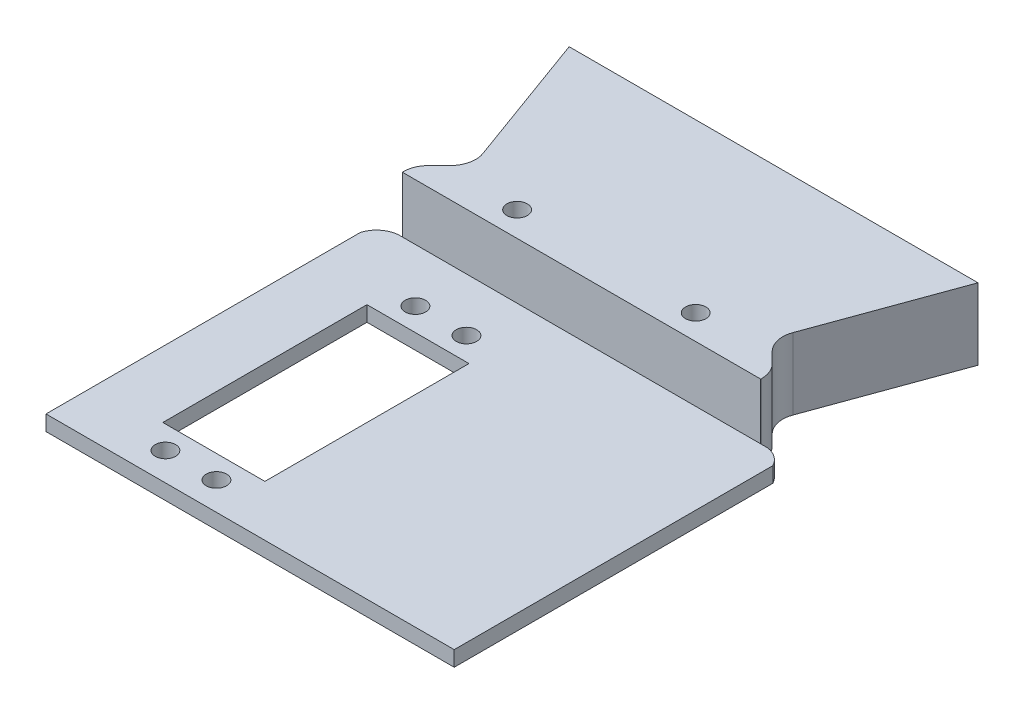
SolidWorks part; units mm, degrees
ref_plane "Front Plane" through (0, 0, 0) normal (0, 0, 1) x (1, 0, 0)
ref_plane "Top Plane" through (0, 0, 0) normal (0, 1, 0) x (1, 0, 0)
ref_plane "Right Plane" through (0, 0, 0) normal (1, 0, 0) x (0, 0, -1)
sketch "Sketch1" plane through (0, 0, 0) normal (0, 1, 0) x (1, 0, 0)
  line L0 (-17.5, 0) -> (17.5, 0) construction
  line L2 (-30.3893, 6.1749) -> (-40.0654, 32.76)
  line L3 (-40.0654, 32.76) -> (40.0654, 32.76)
  line L4 (40.0654, 32.76) -> (30.3893, 6.1749)
  line L5 (-35.1226, -23.3107) -> (-35.1226, -4.7122)
  line L6 (-35.1226, -23.3107) -> (35.1226, -23.3107)
  line L8 (-33.6581, -1.1767) -> (-31.5522, 0.9293)
  line L9 (35.1226, -23.3107) -> (35.1226, -4.7122)
  line L10 (33.6581, -1.1767) -> (31.5522, 0.9293)
  arc A2 (-31.5522, 0.9293) -> (-30.3893, 6.1749) centre (-35.0877, 4.4648) ccw
  arc A3 (-35.1226, -4.7122) -> (-33.6581, -1.1767) centre (-30.1226, -4.7122) cw
  arc A4 (35.1226, -4.7122) -> (33.6581, -1.1767) centre (30.1226, -4.7122) ccw
  arc A5 (31.5522, 0.9293) -> (30.3893, 6.1749) centre (35.0877, 4.4648) cw
  dimension "D5" = 5
  dimension "D6" = 5
  dimension "D7" = 18.5985
  dimension "D8" = 30.1226
  dimension "D19" = 5
  dimension "D20" = 5
  dimension "D1" = 35
  dimension "D2" = 17.5
  dimension "D3" = 23.3107
  dimension "D4" = 18.5985
  dimension "D9" = 30.1226
  dimension "D10" = 4.7122
  dimension "D11" = 5
  dimension "D12" = 32.76
  dimension "D13" = 70
  dimension "D14" = 70
  dimension "D15" = 28.2913
  dimension "D16" = 28.2913
  dimension "D17" = 2.9782
  dimension "D18" = 2.9782
extrude "Boss-Extrude1" add sketch "Sketch1" along normal blind 3
sketch "Sketch8" plane through (0, 3, 0) normal (0, 1, 0) x (1, 0, 0)
  line L0 (-35.1226, -23.3107) -> (35.1226, -23.3107) construction
  line L1 (-35.1226, -23.3107) -> (35.1226, -23.3107)
  line L2 (-35.1226, -23.3107) -> (-25.1226, -33.3107)
  line L3 (-25.1226, -33.3107) -> (25.1226, -33.3107)
  line L4 (25.1226, -33.3107) -> (35.1226, -23.3107)
  dimension "D1" = 10
  dimension "D2" = 45
  dimension "D3" = 45
extrude "Boss-Extrude5" add sketch "Sketch8" against normal blind 3
sketch "Croquis1" plane through (0, 3, 0) normal (0, 1, 0) x (1, 0, 0)
  line L0 (-40.0654, 32.76) -> (40.0654, 32.76) construction
  line L1 (0, 32.76) -> (0, 0) construction
  line L2 (0, 0) -> (-17.5, 0) construction
  line L3 (0, 0) -> (17.5, 0) construction
  circle A0 centre (-17.5, 0) radius 2
  circle A1 centre (17.5, 0) radius 2
  dimension "D4" = 4
  dimension "D5" = 4
  dimension "D1" = 32.76
  dimension "D2" = 17.5
  dimension "D3" = 17.5
extrude "Cortar-Extruir1" cut sketch "Croquis1" against normal blind 10
sketch "Croquis2" plane through (0, 3, 0) normal (0, 1, 0) x (1, 0, 0)
  line L1 (17, -36.0007) -> (40.0026, -36.0007)
  line L2 (40.0026, -36.0007) -> (40.0026, -33.0007)
  line L7 (17, -36.0007) -> (-40, -36.0007)
  line L8 (-40, -36.0007) -> (-40, -4.8773)
  line L9 (-40, -4.8773) -> (40.0026, -4.8773)
  line L10 (40.0026, -4.8773) -> (40.0026, -33.0007)
  line L13 (35.1226, -23.3107) -> (35.1226, -4.7122) construction
  dimension "D6" = 4.88
extrude "Saliente-Extruir1" add sketch "Croquis2" against normal up to surface (3 mm away) up to face at (-17.5, 0, 2)
sketch "Croquis3" plane through (0, 3, 0) normal (0, 1, 0) x (1, 0, 0)
  line L0 (-40, -4.8773) -> (-40, -36.0007) construction
  line L2 (40.0026, -36.0007) -> (40.0026, -4.8773) construction
  line L3 (40.0026, -4.8773) -> (35.1226, -4.8773) construction
  line L4 (40.0026, -36.0007) -> (40.0026, -4.8773)
  line L5 (40.0026, -4.8773) -> (35.1226, -4.8773)
  arc A0 (-35.1226, -4.8773) -> (-40, -9.3921) centre (-35.3039, -9.5734) ccw
  arc A1 (35.1226, -4.8773) -> (40.0026, -7.3959) centre (35.8131, -9.5263) cw
  line M1 (40.0026, -4.8773) -> (35.1226, -4.8773)
  dimension "D1" = 4.6996
  dimension "D2" = 4.7
extrude "Cortar-Extruir2" cut sketch "Croquis3" against normal blind 10 and the other way through all contours A1 L4 M1 region at (39.0792, 3, 5.5854)
sketch "Croquis4" plane through (0, 3, 0) normal (0, 1, 0) x (1, 0, 0)
  line L0 (-40, -4.8773) -> (-40, -36.0007) construction
  line L1 (-35.1226, -4.8773) -> (-40, -4.8773) construction
  line L2 (-35.1226, -4.8773) -> (-40, -4.8773)
  line L3 (-40, -4.8773) -> (-40, -36.0007)
  arc A0 (-35.1226, -4.8773) -> (-40, -8.2239) centre (-35.4947, -9.5625) ccw
  line M20 (-40, -4.8773) -> (-40, -36.0007)
  dimension "D1" = 4.7
extrude "Cortar-Extruir3" cut sketch "Croquis4" against normal blind 10 contours A0 L2 M20 region at (-38.9852, 3, 5.7663)
sketch "Croquis6" plane through (0, 3, 0) normal (0, 1, 0) x (1, 0, 0)
  line L0 (-35.1226, -4.8773) -> (35.1226, -4.8773)
  line L1 (-40.0654, 32.76) -> (-30.3893, 6.1749) construction
  line L2 (-31.5522, 0.9293) -> (-33.6581, -1.1767) construction
  line L3 (-40.0654, 32.76) -> (-30.3893, 6.1749)
  line L4 (-31.5522, 0.9293) -> (-33.6581, -1.1767)
  line L5 (33.6581, -1.1767) -> (31.5522, 0.9293) construction
  line L6 (30.3893, 6.1749) -> (40.0654, 32.76) construction
  line L7 (33.6581, -1.1767) -> (31.5522, 0.9293)
  line L8 (30.3893, 6.1749) -> (40.0654, 32.76)
  line L9 (35.1226, -4.8773) -> (35.1226, -4.7122) construction
  line L10 (35.1226, -4.8773) -> (35.1226, -4.7122)
  line L11 (-35.1226, -4.7122) -> (-35.1226, -4.8773) construction
  line L12 (-35.1226, -4.7122) -> (-35.1226, -4.8773)
  arc A0 (-31.5522, 0.9293) -> (-30.3893, 6.1749) centre (-35.0877, 4.4648) ccw construction
  arc A1 (-33.6581, -1.1767) -> (-35.1226, -4.7122) centre (-30.1226, -4.7122) ccw construction
  arc A2 (-31.5522, 0.9293) -> (-30.3893, 6.1749) centre (-35.0877, 4.4648) ccw
  arc A3 (-33.6581, -1.1767) -> (-35.1226, -4.7122) centre (-30.1226, -4.7122) ccw
  arc A4 (35.1226, -4.7122) -> (33.6581, -1.1767) centre (30.1226, -4.7122) ccw construction
  arc A5 (30.3893, 6.1749) -> (31.5522, 0.9293) centre (35.0877, 4.4648) ccw construction
  arc A6 (35.1226, -4.7122) -> (33.6581, -1.1767) centre (30.1226, -4.7122) ccw
  arc A7 (30.3893, 6.1749) -> (31.5522, 0.9293) centre (35.0877, 4.4648) ccw
  circle A8 centre (-16.7158, 19.9949) radius 9.4109
  circle M2 centre (17.5, 0) radius 2
  circle M3 centre (-17.5, 0) radius 2
  line M11 (35.1226, -4.8773) -> (35.1226, -4.7122)
  arc M12 (35.1226, -4.7122) -> (33.6581, -1.1767) centre (30.1226, -4.7122) ccw
  line M13 (33.6581, -1.1767) -> (31.5522, 0.9293)
  arc M14 (31.5522, 0.9293) -> (30.3893, 6.1749) centre (35.0877, 4.4648) cw
  line M15 (30.3893, 6.1749) -> (40.0654, 32.76)
  line M16 (40.0654, 32.76) -> (-40.0654, 32.76)
  line M17 (-40.0654, 32.76) -> (-30.3893, 6.1749)
  arc M18 (-30.3893, 6.1749) -> (-31.5522, 0.9293) centre (-35.0877, 4.4648) cw
  line M19 (-31.5522, 0.9293) -> (-33.6581, -1.1767)
  arc M20 (-33.6581, -1.1767) -> (-35.1226, -4.7122) centre (-30.1226, -4.7122) ccw
  line M21 (-35.1226, -4.7122) -> (-35.1226, -4.8773)
extrude "Saliente-Extruir2" add sketch "Croquis6" along normal blind 11 contours L0 A8 M21 M11 M12 M13 M14 M15 M16 M17 M18 M19 M20 M3 M2 | A8 region at (2.0372, 3, -14.179) region at (-16.7158, 3, -19.9949)
sketch "Croquis8" plane through (0, 0, 36.0007) normal (0, 0, 1) x (1, 0, 0)
  line L1 (-40, 3) -> (40.0026, 3)
  line L2 (-40, 3) -> (-40, 0)
  line L3 (-40, 0) -> (40.0026, 0)
  line L4 (40.0026, 3) -> (40.0026, 0)
extrude "Saliente-Extruir3" add sketch "Croquis8" along normal blind 33.83
sketch "Croquis9" plane through (0, 3, 0) normal (0, 1, 0) x (1, 0, 0)
  line L0 (-40, -69.8307) -> (0.0013, -69.8307) construction
  line L1 (40.0026, -69.8307) -> (-40, -69.8307) construction
  line L2 (0.0013, -69.8307) -> (0.0013, -29.8307) construction
  line L3 (0.0013, -29.8307) -> (-17.1, -29.8307) construction
  line L4 (-17.1, -29.8307) -> (-17.1, -12.8307) construction
  line L5 (-26.6, -66.8307) -> (-22.1, -66.8307) construction
  line L6 (-17.1, -66.8307) -> (-27.1, -66.8307)
  line L7 (-17.1, -66.8307) -> (-7.1, -66.8307)
  line L8 (-26.6, -66.8307) -> (-7.6, -66.8307)
  line L9 (-27.1, -66.8307) -> (-7.1, -66.8307)
  line L10 (-27.1, -59.8307) -> (-27.1, -19.8307)
  line L11 (-26.6, -12.8307) -> (-7.6, -12.8307)
  line L12 (-7.1, -59.8307) -> (-7.1, -19.8307)
  line L13 (-26.6, -66.8307) -> (-26.6, -59.8307)
  line L14 (-26.6, -59.8307) -> (-7.6, -59.8307)
  line L15 (-7.6, -66.8307) -> (-7.6, -59.8307)
  line L16 (-22.1, -66.8307) -> (-22.1, -64.3307) construction
  line L17 (-17.1, -66.8307) -> (-17.1, -59.8307) construction
  line L18 (-26.6, -12.8307) -> (-22.1, -12.8307) construction
  line L19 (-26.6, -12.8307) -> (-7.6, -12.8307)
  line L20 (-26.6, -12.8307) -> (-26.6, -19.8307)
  line L21 (-26.6, -19.8307) -> (-7.6, -19.8307)
  line L22 (-7.6, -12.8307) -> (-7.6, -19.8307)
  line L23 (-22.1, -12.8307) -> (-22.1, -15.3307) construction
  line L24 (-26.6, -59.8307) -> (-27.1, -59.8307)
  line L25 (-7.6, -59.8307) -> (-7.1, -59.8307)
  line L26 (-26.6, -19.8307) -> (-27.1, -19.8307)
  line L27 (-7.6, -19.8307) -> (-7.1, -19.8307)
  line L28 (-40, -8.2239) -> (-40, -69.8307) construction
  circle A0 centre (-17.1, -29.8307) radius 1.5
  circle A1 centre (-22.1, -64.3307) radius 2
  circle A2 centre (-12.1, -64.3307) radius 2
  circle A3 centre (-22.1, -15.3307) radius 2
  circle A4 centre (-12.1, -15.3307) radius 2
  point P18 (-26.6, -63.3307)
  dimension "D7" = 3
  dimension "D13" = 4
  dimension "D19" = 4
  dimension "D1" = 40
  dimension "D3" = 17
  dimension "D4" = 37
  dimension "D5" = 10
  dimension "D6" = 10
  dimension "D8" = 0.5
  dimension "D9" = 0.5
  dimension "D10" = 7
  dimension "D11" = 4.5
  dimension "D12" = 2.5
  dimension "D14" = 0.5
  dimension "D15" = 0.5
  dimension "D16" = 7
  dimension "D17" = 4.5
  dimension "D18" = 2.5
  dimension "D20" = 12.9
  dimension "D21" = 10
extrude "Cortar-Extruir7" cut sketch "Croquis9" against normal blind 33.83 contours L27 L21 L26 L10 L24 L14 L25 L12 A0 | A0 region at (-17.1, 3, 39.9199) region at (-17.1, 3, 29.8307)
extrude "Cortar-Extruir8" cut sketch "Croquis9<3>" against normal blind 33.83 contours A3 | A4 | A1 | A2 region at (-22.1, 3, 64.3307) region at (-12.1, 3, 64.3307) region at (-22.1, 3, 15.3307) region at (-12.1, 3, 15.3307)
sketch "Croquis9<3>" plane through (0, 3, 0) normal (0, 1, 0) x (1, 0, 0) same geometry as "Croquis9"
